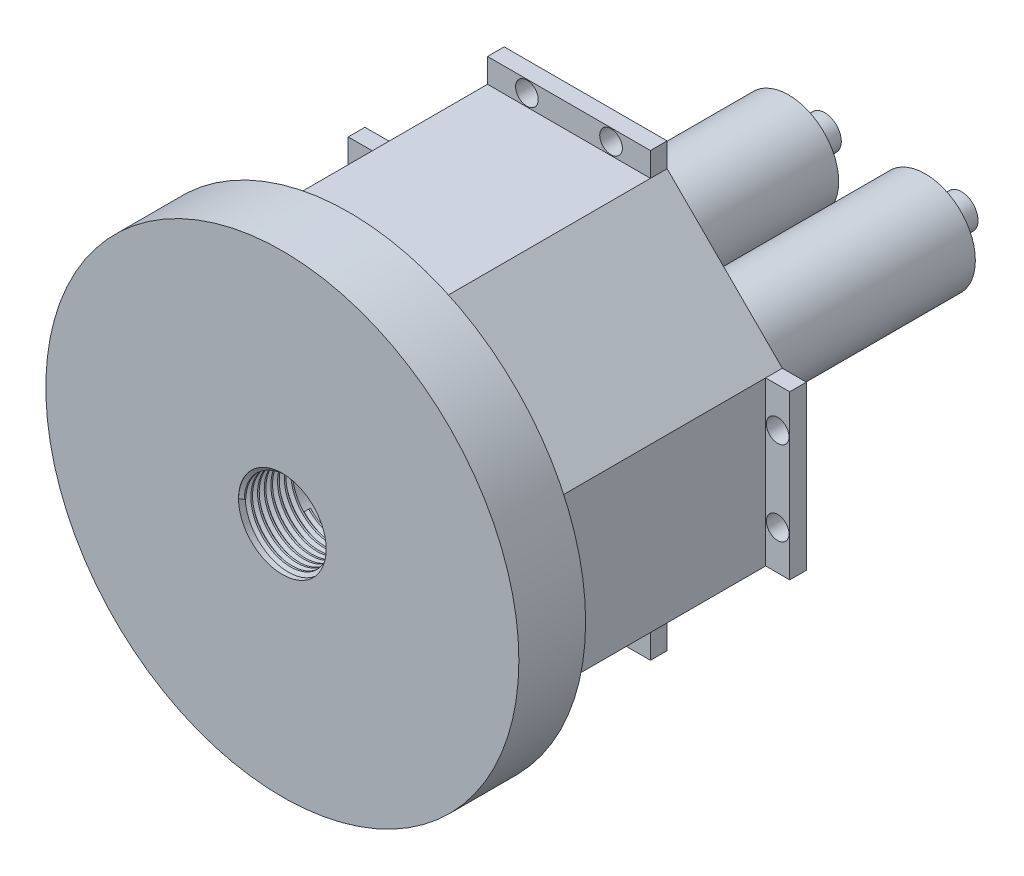
SolidWorks part; units mm, degrees
material "6061 Alloy"
ref_plane "Front Plane" through (0, 0, 0) normal (0, 0, 1) x (1, 0, 0)
ref_plane "Top Plane" through (0, 0, 0) normal (0, 1, 0) x (1, 0, 0)
ref_plane "Right Plane" through (0, 0, 0) normal (1, 0, 0) x (0, 0, -1)
sketch "Sketch1" plane through (0, 0, 0) normal (0, 0, 1) x (1, 0, 0)
  line L0 (0, 39.7082) -> (0, 0) construction
  line L1 (-15.4983, 42) -> (15.4983, 42)
  line L2 (-15.4983, 42) -> (-15.4983, 37.4163)
  line L3 (-15.4983, 37.4163) -> (15.4983, 37.4163)
  line L4 (15.4983, 42) -> (15.4983, 37.4163)
  line L5 (-15.4983, 42) -> (15.4983, 37.4163) construction
  line L6 (-15.4983, 37.4163) -> (15.4983, 42) construction
  line L7 (-15.4983, -42) -> (15.4983, -42)
  line L8 (-15.4983, -42) -> (-15.4983, -37.4163)
  line L9 (-15.4983, -37.4163) -> (15.4983, -37.4163)
  line L10 (15.4983, -42) -> (15.4983, -37.4163)
  line L11 (-15.4983, -42) -> (15.4983, -37.4163) construction
  line L12 (-15.4983, -37.4163) -> (15.4983, -42) construction
  line L13 (0, 0) -> (0, -39.7082) construction
  line L14 (0, 0) -> (-39.7082, 0) construction
  line L15 (0, 0) -> (39.7082, 0) construction
  line L17 (-42, 15.4983) -> (-37.4163, 15.4983)
  line L18 (-42, 15.4983) -> (-42, -15.4983)
  line L19 (-42, -15.4983) -> (-37.4163, -15.4983)
  line L20 (-37.4163, 15.4983) -> (-37.4163, -15.4983)
  line L21 (-42, 15.4983) -> (-37.4163, -15.4983) construction
  line L22 (-42, -15.4983) -> (-37.4163, 15.4983) construction
  line L23 (37.4163, 15.4983) -> (42, 15.4983)
  line L24 (37.4163, 15.4983) -> (37.4163, -15.4983)
  line L25 (37.4163, -15.4983) -> (42, -15.4983)
  line L26 (42, 15.4983) -> (42, -15.4983)
  line L27 (37.4163, 15.4983) -> (42, -15.4983) construction
  line L28 (37.4163, -15.4983) -> (42, 15.4983) construction
  line L29 (-15.4983, 37.4163) -> (-37.4163, 15.4983)
  line L30 (-37.4163, 15.4983) -> (-37.4163, -15.4983)
  line L31 (-37.4163, -15.4983) -> (-15.4983, -37.4163)
  line L32 (-15.4983, -37.4163) -> (15.4983, -37.4163)
  line L33 (15.4983, -37.4163) -> (37.4163, -15.4983)
  line L34 (37.4163, -15.4983) -> (37.4163, 15.4983)
  line L35 (37.4163, 15.4983) -> (15.4983, 37.4163)
  line L36 (15.4983, 37.4163) -> (-15.4983, 37.4163)
  circle A0 centre (0, 0) radius 37.4163 construction
  point P0 (0, 39.7082)
  point P5 (0, -39.7082)
  dimension "D1" = 84
extrude "Boss-Extrude1" add sketch "Sketch1" along normal blind 45.0088 contours L24 L35 L3 L29 L20 L31 L9 L33 region at (0, 0, 0)
extrude "Boss-Extrude2" add sketch "Sketch1<3>" along normal blind 3.175 contours L31 L30 L29 L20 L17 L18 L19 | L33 L32 L31 L9 L8 L7 L10 | L35 L34 L33 L24 L25 L26 L23 | L36 L35 L3 L4 L1 L2 L29 region at (0, 39.7082, 0) region at (-39.7082, 0, 0) region at (39.7082, 0, 0) region at (0, -39.7082, 0)
sketch "Sketch1<3>" plane through (0, 0, 0) normal (0, 0, 1) x (1, 0, 0) same geometry as "Sketch1"
sketch "Sketch2" plane through (0, 0, 0) normal (0, 0, -1) x (-1, 0, 0)
  line L0 (-13.0048, 0) -> (0, 0) construction
  line L1 (0, 0) -> (13.0048, 0) construction
  circle A0 centre (-13.0048, 0) radius 9.525
  circle A1 centre (13.0048, 0) radius 9.525
  dimension "D2" = 19.05
  dimension "D1" = 26.0096
extrude "Boss-Extrude3" add sketch "Sketch2" along normal blind 51.6128
sketch "Sketch3" plane through (0, 0, -51.6128) normal (0, 0, -1) x (-1, 0, 0)
  circle A0 centre (-13.0048, 0) radius 3.175
  circle A1 centre (13.0048, 0) radius 3.175
  dimension "D1" = 6.35
extrude "Boss-Extrude4" add sketch "Sketch3" along normal blind 6.858
sketch "Sketch4" plane through (0, 0, 0) normal (0, 0, -1) x (-1, 0, 0)
  line L0 (-15.4983, -39.7082) -> (15.4983, -39.7082) construction
  line L1 (-15.4983, -42) -> (-15.4983, -37.4163) construction
  line L2 (-39.7082, 15.4983) -> (-39.7082, -15.4983) construction
  line L3 (-37.4163, 15.4983) -> (-42, 15.4983) construction
  line L4 (-37.4163, -15.4983) -> (-42, -15.4983) construction
  line L5 (-15.4983, 39.7082) -> (15.4983, 39.7082) construction
  line L6 (-15.4983, 42) -> (-15.4983, 37.4163) construction
  line L7 (15.4983, 42) -> (15.4983, 37.4163) construction
  line L8 (15.4983, -42) -> (15.4983, -37.4163) construction
  line L9 (39.7082, -15.4983) -> (39.7082, 15.4983) construction
  line L10 (42, -15.4983) -> (37.4163, -15.4983) construction
  line L11 (42, 15.4983) -> (37.4163, 15.4983) construction
  line L12 (-39.7082, 8.001) -> (-39.7082, -8.001)
  line L13 (-8.001, -39.7082) -> (8.001, -39.7082)
  line L14 (39.7082, 8.001) -> (39.7082, -8.001)
  line L15 (-8.001, 39.7082) -> (8.001, 39.7082)
  line L16 (-39.7082, 0) -> (0, 0)
  line L17 (0, 0) -> (0, 39.7082)
  line L18 (0, 0) -> (39.7082, 0)
  line L19 (0, 0) -> (0, -39.7082)
  circle A0 centre (-39.7082, 8.001) radius 2.1527
  circle A1 centre (-39.7082, -8.001) radius 2.1527
  circle A2 centre (-8.001, -39.7082) radius 2.1527
  circle A3 centre (8.001, -39.7082) radius 2.1526
  circle A4 centre (39.7082, -8.001) radius 2.1527
  circle A5 centre (39.7082, 8.001) radius 2.1527
  circle A6 centre (8.001, 39.7082) radius 2.1527
  circle A7 centre (-8.001, 39.7082) radius 2.1527
  point P40 (-39.7082, 0)
  point P41 (39.7082, 0)
  dimension "D3" = 4.3053
  dimension "D1" = 16.002
  dimension "D2" = 16.002
extrude "Cut-Extrude1" cut sketch "Sketch4" against normal through all contours A3 | A2 | A1 | A0 | A7 | A6 | A5 | A4 region at (10.0928, 39.7082, 0) region at (-8.001, 41.7999, 0) region at (-38.2291, 9.4801, 0) region at (-41.1873, -6.5219, 0) region at (-8.001, -37.6164, 0) region at (10.0928, -39.7082, 0) region at (38.2291, -6.5219, 0) region at (41.1873, 9.4801, 0)
sketch "Sketch5" plane through (0, 0, 45.0088) normal (0, 0, 1) x (1, 0, 0)
  circle A0 centre (0, 0) radius 45
  dimension "D1" = 90
extrude "Boss-Extrude5" add sketch "Sketch5" along normal blind 12.7 contours A0
sketch "Sketch6" plane through (0, 0, 57.7088) normal (0, 0, 1) x (1, 0, 0)
  circle A0 centre (0, 0) radius 8.34
  dimension "D1" = 16.68
extrude "Cut-Extrude2" cut sketch "Sketch6" against normal blind 12.7 contours A0
thread "Thread1" pitch 1.27 method extrude profile "Thread Profile1" start angle 0, offset 0, length 10, pitch 1.27, diameter 16.68
ref_plane "Plane1" through (-8.34, 0, 57.7088) normal (0, -1, 0) x (-1, 0, 0)
sketch "Thread Profile1" plane through (-8.34, 0, 57.7088) normal (0, -1, 0) x (-1, 0, 0)
  line L0 (0, 0) -> (0, 1.27) construction
  line L11 (0, 0) -> (0, 1.1112)
  line L12 (0, 1.1112) -> (-0.6874, 0.7144)
  line L13 (-0.6874, 0.7144) -> (-0.6874, 0.3969)
  line L15 (-0.6874, 0.3969) -> (0, 0)
  line L17 (-0.6874, 0.5556) -> (0, 0.5556) construction
  point P2 (0, 0)
  dimension "Pitch" = 1.27
  dimension "Profile_Angle" = 60
  dimension "Profile_Land" = 0.3175
  dimension "Profile_Height" = 0.6874
sketch "Sketch10" plane through (0, 0, 45.0088) normal (0, 0, 1) x (1, 0, 0)
  circle A0 centre (0, 0) radius 6.35
extrude "Cut-Extrude3" cut sketch "Sketch10" against normal blind 25.4
